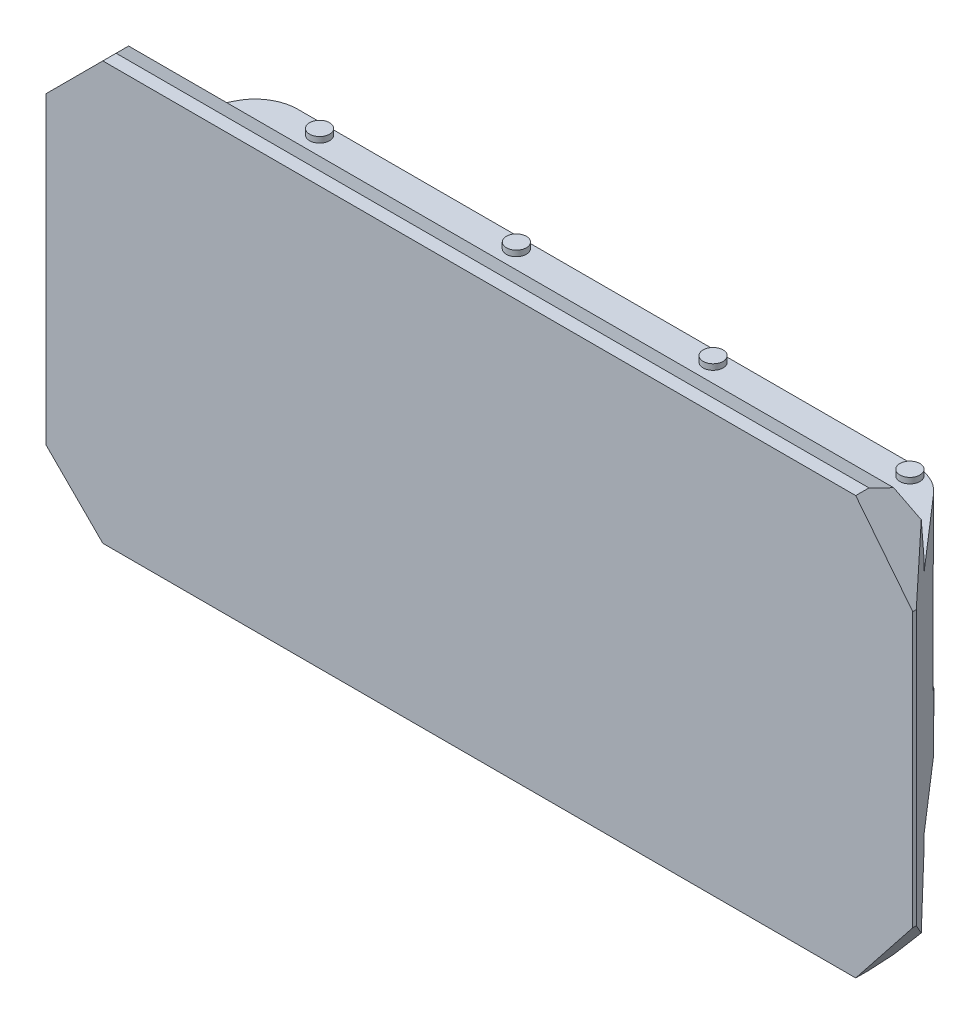
SolidWorks part; units mm, degrees
ref_plane "Alzado" through (0, 0, 0) normal (0, 0, 1) x (1, 0, 0)
ref_plane "Planta" through (0, 0, 0) normal (0, 1, 0) x (1, 0, 0)
ref_plane "Vista lateral" through (0, 0, 0) normal (1, 0, 0) x (0, 0, -1)
sketch "Sketch1" plane through (0, 0, 0) normal (0, 1, 0) x (1, 0, 0)
  line L0 (0, 0) -> (-2143.7202, 0) construction
  line L1 (1320, 732.5) -> (-1320, 732.5)
  line L3 (1320, -732.5) -> (-1520, -732.5) construction
  line L5 (1520, 732.5) -> (-1520, -732.5) construction
  line L6 (1520, -732.5) -> (-1520, 732.5) construction
  line L11 (0, 0) -> (2435.9768, 0) construction
  line L14 (1320, 732.5) -> (1520, 532.5)
  line L15 (1520, -532.5) -> (1320, -732.5)
  line L16 (1520, 532.5) -> (1520, -532.5)
  line L17 (-1520, 0) -> (-1520, -480)
  line L18 (-1520, 0) -> (-1520, 480)
  line L19 (-1520, -732.5) -> (-1320, -732.5) construction
  line L20 (-1320, -732.5) -> (-1520, -480)
  line L21 (-1320, -732.5) -> (-1320, 941.145) construction
  line L22 (-1520, 480) -> (-1320, 732.5)
  line L24 (-1320, -732.5) -> (1320, -732.5)
  point P0 (0, 0)
  point P15 (0, 0)
  dimension "D1" = 1465
  dimension "D2" = 3040
  dimension "D3" = 480
  dimension "D4" = 200
extrude "Boss-Extrude1" add sketch "Sketch1" along normal blind 530
sketch "Sketch2" plane through (0, 530, 0) normal (0, 1, 0) x (1, 0, 0)
  line L10 (-1520, 480) -> (-1520, -480) construction
  line L11 (-1070, 2000) -> (-1970, 2000)
  line L13 (-1070, 2000) -> (-1070, -2000)
  line L14 (-1070, -2000) -> (-1970, -2000)
  line L15 (-1970, 2000) -> (-1970, -2000)
  line L16 (-1070, 2000) -> (-1970, -2000) construction
  line L17 (-1070, -2000) -> (-1970, 2000) construction
  point P0 (-1520, 0)
  dimension "D1" = 4000
  dimension "D2" = 450
extrude "Cut-Extrude1" cut sketch "Sketch2" against normal blind 530 draft 41
sketch "Sketch4" plane through (0, 530, 0) normal (0, 1, 0) x (1, 0, 0)
  line L0 (1520, -532.5) -> (1520, 532.5) construction
  line L1 (1260, 2000) -> (1780, 2000)
  line L2 (1260, 2000) -> (1260, -2000)
  line L3 (1260, -2000) -> (1780, -2000)
  line L4 (1780, 2000) -> (1780, -2000)
  line L5 (1260, 2000) -> (1780, -2000) construction
  line L6 (1260, -2000) -> (1780, 2000) construction
  point P0 (1520, 0)
  dimension "D1" = 4000
  dimension "D2" = 260
extrude "Cut-Extrude2" cut sketch "Sketch4" against normal blind 813 draft 26
ref_plane "Plane1" through (1720, 0, 0) normal (1, 0, 0) x (0, 0, -1)
sketch "Sketch6" plane through (1720, 0, 0) normal (1, 0, 0) x (0, 0, -1)
  line L0 (0, 0) -> (0, 704.3886) construction
  line L8 (-732.5, 530) -> (-732.5, 46.5692)
  line L9 (732.5, 406.9818) -> (732.5, 0) construction
  line L10 (397.5, 530) -> (397.5, 216.71)
  line L11 (732.5, 530) -> (-732.5, 530) construction
  line L12 (534.0017, 0) -> (-534.0017, 0) construction
  line L13 (732.5, 46.5692) -> (708.6379, 114.2945)
  line L14 (397.5, 216.71) -> (450.9514, 216.71)
  line L15 (450.9514, 216.71) -> (708.6379, 114.2945)
  line L16 (397.5, 530) -> (732.5, 530)
  line L17 (732.5, 530) -> (732.5, 46.5692)
  line L18 (-397.5, 530) -> (-732.5, 530)
  line L19 (-450.9514, 216.71) -> (-708.6379, 114.2945)
  line L20 (-397.5, 216.71) -> (-450.9514, 216.71)
  line L21 (-732.5, 46.5692) -> (-708.6379, 114.2945)
  line L22 (-397.5, 530) -> (-397.5, 216.71)
  dimension "D1" = 397.5
  dimension "D2" = 216.71
extrude "Cut-Extrude4" cut sketch "Sketch6" against normal through all
sketch "Sketch7" plane through (1720, 0, 0) normal (1, 0, 0) x (0, 0, -1)
  line L0 (397.5, 530) -> (-397.5, 530) construction
  line L3 (185, 456.62) -> (-185, 456.62)
  line L5 (185, 603.38) -> (-185, 456.62) construction
  line L6 (185, 456.62) -> (-185, 603.38) construction
  line L7 (-185, 456.62) -> (-228, 530)
  line L8 (185, 456.62) -> (228, 530)
  line L9 (-228, 530) -> (-228, 603.38)
  line L10 (-228, 603.38) -> (228, 603.38)
  line L11 (228, 603.38) -> (228, 530)
  point P0 (0, 530)
  dimension "D1" = 370
  dimension "D2" = 73.38
extrude "Cut-Extrude6" cut sketch "Sketch7" against normal through all
ref_plane "Plane2" through (0, 0, -397.5) normal (0, 0, -1) x (-1, 0, 0)
sketch "Sketch8" plane through (0, 0, -397.5) normal (0, 0, -1) x (-1, 0, 0)
  circle A0 centre (-1050, 490) radius 35
  circle A1 centre (-360, 490) radius 35
  circle A2 centre (330, 490) radius 35
  circle A3 centre (1020, 490) radius 35
  dimension "D3" = 70
  dimension "D1" = 490
  dimension "D2" = 500
  dimension "D5" = 690
  dimension "D4" = 4
extrude "Boss-Extrude2" add sketch "Sketch8" along normal blind 20
ref_plane "Plane4" through (0, 0, 0) normal (0, 0, 1) x (1, 0, 0)
mirror "Mirror1" about plane through (0, 0, 0) normal (0, 0, 1) of "Boss-Extrude2"
fillet "Fillet2" radius 150 3 edges at (1260, 530, 312.75) (-1070, 530, -312.75) (-1070, 530, 312.75)
ref_plane "Plane7" through (0, 0, 0) normal (0, -1, 0) x (-1, 0, 0)
ref_plane "Plane8" through (0, 0, 0) normal (-1, 0, 0) x (0, 0, 1)
sketch "Sketch9" plane through (0, 0, -417.5) normal (0, 0, -1) x (-1, 0, 0)
  line L0 (330, 490) -> (675, 490) construction
  point P4 (0, 0)
  dimension "D1" = 345
move or copy body "Body-Move/Copy3" bodies to move or copy 109 copy no rotation origin (0, 265, 0) rotation axis (1, 0, 0) rotation angle 180
move or copy body "Body-Move/Copy4" bodies to move or copy 117 copy no rotation origin (-0.7509, 0, 0) rotation axis (0, 1, 0) rotation angle 180
move or copy body "Body-Move/Copy5" bodies to move or copy 118 copy no rotation origin (0, 265, 0) rotation axis (1, 0, 0) rotation angle 90
